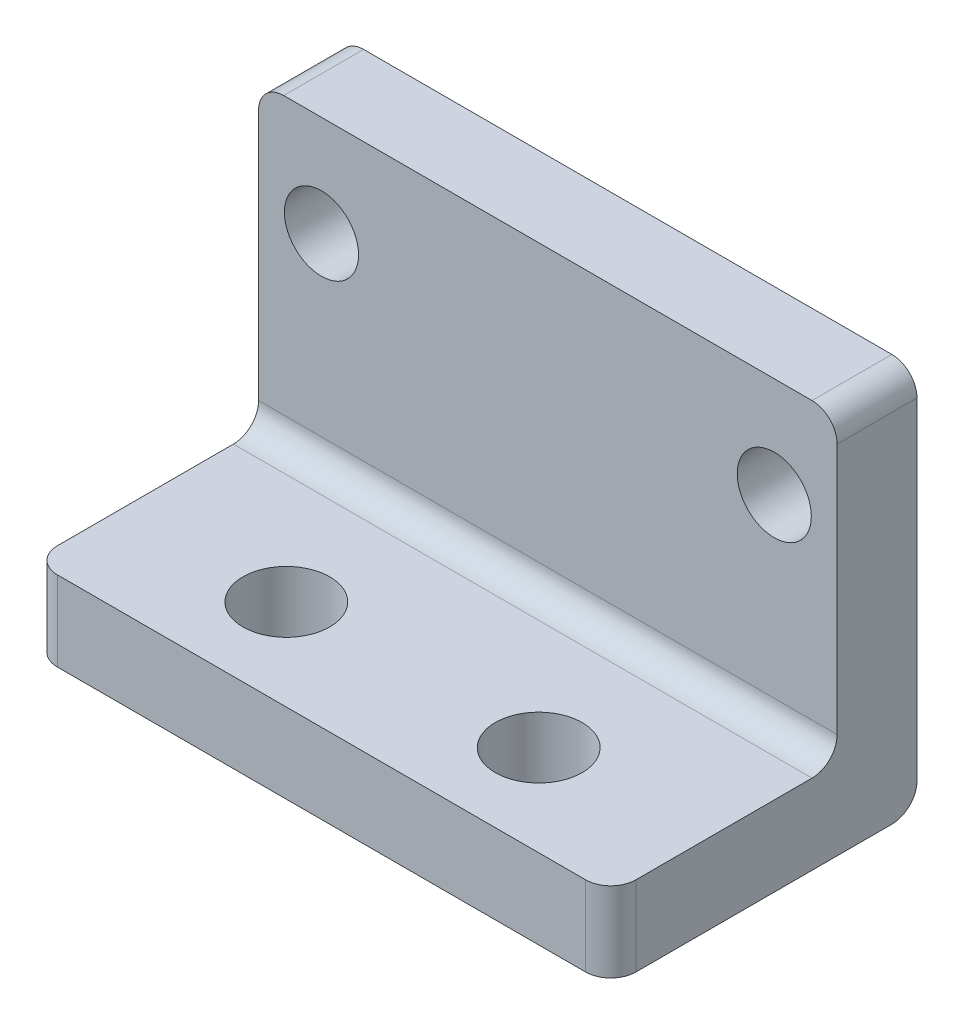
SolidWorks part; units mm, degrees
ref_plane "Front Plane" through (0, 0, 0) normal (0, 0, 1) x (1, 0, 0)
ref_plane "Top Plane" through (0, 0, 0) normal (0, 1, 0) x (1, 0, 0)
ref_plane "Right Plane" through (0, 0, 0) normal (1, 0, 0) x (0, 0, -1)
sketch "Sketch1" plane through (0, 0, 0) normal (0, 0, 1) x (1, 0, 0)
  line L0 (0, -10) -> (23, -10)
  line L1 (0, 0) -> (23, 0)
  line L2 (0, 0) -> (0, -13.175)
  line L3 (0, -13.175) -> (23, -13.175)
  line L4 (23, 0) -> (23, -13.175)
  line L5 (0, 0) -> (0, 2)
  line L6 (0, 2) -> (23, 2)
  line L7 (23, 2) -> (23, 0)
  circle A0 centre (2.5, -2) radius 1.4732
  circle A1 centre (20.5, -2) radius 1.4732
  dimension "D2" = 2.9464
  dimension "D1" = 18
  dimension "D4" = 3.175
  dimension "D5" = 23
  dimension "D6" = 2.5
  dimension "D7" = 2
  dimension "D3" = 10
  dimension "D8" = 2
extrude "Boss-Extrude1" add sketch "Sketch1" along normal blind 3.175 contours L4 L1 L2 L0 A1 A0 | L4 L0 L2 L3 | L7 L6 L5 L1 region at (11.5, -5.1891, 0) region at (11.5, -11.5875, 0) region at (11.5, 1, 0)
extrude "Boss-Extrude2" add sketch "Sketch1<3>" along normal blind 9 from surface contours L4 L0 L2 L3 region at (11.5, -11.5875, 0) starting at face at (21.9732, -2, 3.175)
sketch "Sketch1<3>" plane through (0, 0, 0) normal (0, 0, 1) x (1, 0, 0) same geometry as "Sketch1"
sketch "Mount Hole Location" plane through (0, -10, 0) normal (0, 1, 0) x (1, 0, 0)
  line L0 (0, -12.175) -> (23, -12.175) construction
  line L1 (8.579, -8.5555) -> (14.421, -8.5555) construction
  line L3 (0, -4.809) -> (23, -4.809) construction
  line L4 (0, -12.175) -> (0, -3.175) construction
  line L5 (23, -12.175) -> (23, -3.175) construction
  line L6 (23, -12.175) -> (0, -12.175) construction
  line L7 (6.4835, -6.46) -> (6.4835, -4.809) construction
  circle A0 centre (16.5165, -8.5555) radius 3.4925 construction
  circle A1 centre (16.5165, -8.5555) radius 2.0955
  circle A2 centre (6.4835, -8.5555) radius 2.0955
  circle A3 centre (6.4835, -8.5555) radius 3.4925 construction
  point P0 (11.5, -8.5555)
  point P4 (11.5, -12.175)
  point P15 (11.5, -8.5555)
  dimension "D2" = 6.985
  dimension "D3" = 4.191
  dimension "D1" = 1.651
  dimension "D4" = 5.842
  dimension "D5" = 7.366
hole_wizard "#8-32 Tapped Hole1" positions "3DSketch1" profile "Sketch3" tap size "#8-32" standard "ANSI Inch" end condition through all
sketch3d "3DSketch1"
  point P5 (6.4835, -10, 8.5555)
  point P8 (16.5165, -10, 8.5555)
sketch "Sketch3" plane through (6.4835, -10, 8.5555) normal (1, 0, 0) x (0, 0, 1)
  line L0 (0, 0) -> (0, 3.175)
  line L1 (0, 3.175) -> (1.7272, 3.175)
  line L2 (1.7272, 3.175) -> (1.7272, 0)
  line L5 (1.7272, 0) -> (0, 0)
  line L11 (0, -6.35) -> (0, 107.95) construction
  dimension "Thru Tap Drill Dia." = 3.4544
  dimension "Thru Tap Drill Depth" = 3.175
cosmetic thread "Hole Thread1"
cosmetic thread "Hole Thread2"
fillet "Fillet1" radius 1 6 edges at (0, -11.5875, 12.175) (23, -11.5875, 12.175) (11.5, -13.175, 0) (11.5, -10, 3.175) (23, 2, 1.5875) (0, 2, 1.5875)
equation "\"D6@Sketch1\"=(\"D5@Sketch1\"-\"D1@Sketch1\")/2"
